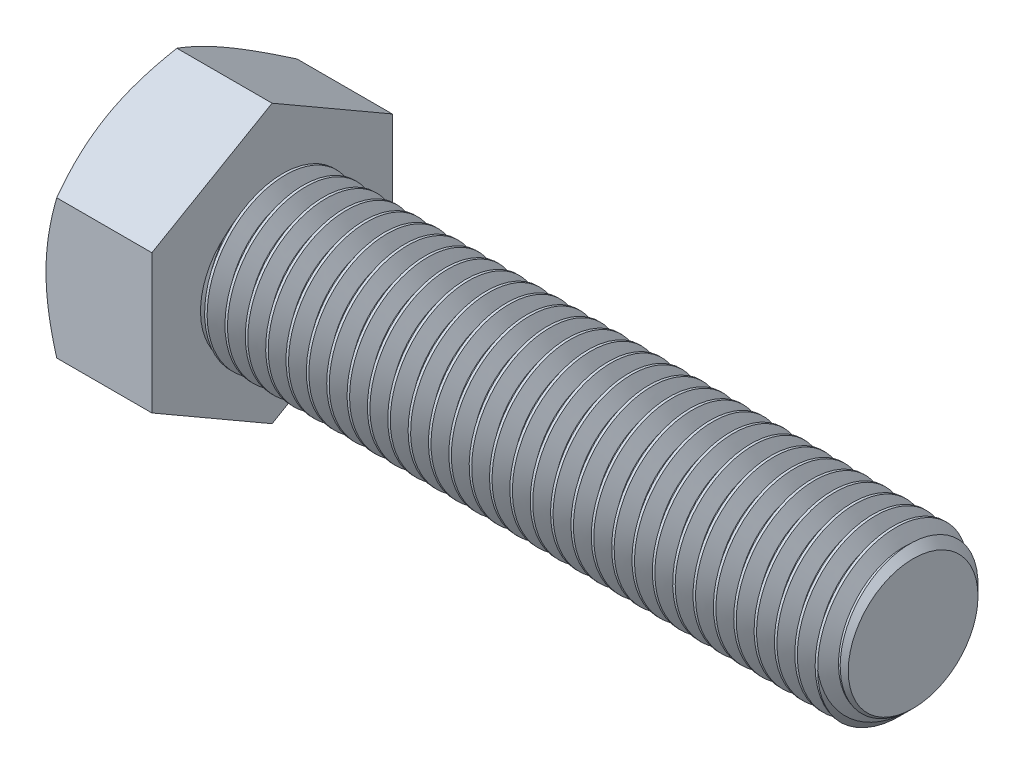
SolidWorks part; units mm, degrees
ref_plane "Front Plane" through (0, 0, 0) normal (0, 0, 1) x (1, 0, 0)
ref_plane "Top Plane" through (0, 0, 0) normal (0, 1, 0) x (1, 0, 0)
ref_plane "Right Plane" through (0, 0, 0) normal (1, 0, 0) x (0, 0, -1)
sketch "Sketch1" plane through (0, 0, 0) normal (0, 0, 1) x (1, 0, 0)
  line L0 (-51.7922, 0) -> (51.7922, 0) construction
  line L1 (51.7922, 11.1125) -> (51.7922, -11.1125) construction
  line L2 (-37.1078, 16.6687) -> (-37.1078, -16.6687) construction
  line L3 (-51.7922, 16.6687) -> (-51.7922, -16.6687) construction
  point P9 (-37.1078, 0)
  point P10 (41.9144, -11.1125)
  dimension "D1" = 9.8778
  dimension "Screw Dia" = 22.225
  dimension "Hex" = 33.3375
  dimension "Head Ht" = 14.6844
  dimension "Screw Lenght" = 88.9
ref_plane "Plane2" through (51.7922, 0, 0) normal (1, 0, 0) x (0, 0, -1)
sketch "Sketch5" plane through (51.7922, 0, 0) normal (1, 0, 0) x (0, 0, -1)
  circle A0 centre (0, 0) radius 11.1125
extrude "Boss-Extrude3" add sketch "Sketch5" against normal up to vertex (88.9 mm away) up to point (-37.1078, 0, 0)
sketch "Sketch9" plane through (51.7922, 0, 0) normal (1, 0, 0) x (0, 0, -1)
  circle A1 centre (0, 0) radius 11.1125
  circle A2 centre (0, 0) radius 11.1125
  dimension "D1" = 0
curve "Helix/Spiral1" pitch 2.8222 height 91.7222 turns 32.5 parameters "Pitch"=2.8222
chamfer "Chamfer1" distance 2.1167 angle 45 1 edges at (51.7922, 0, -11.1125)
sketch "Sketch10" plane through (0, 0, 0) normal (0, 0, 1) x (1, 0, 0)
  line L0 (51.7922, 11.1125) -> (52.8505, 9.2794)
  line L1 (52.8505, 9.2794) -> (53.2033, 9.2794)
  line L2 (53.2033, 9.2794) -> (54.2616, 11.1125)
  line L3 (51.7922, 11.1125) -> (54.2616, 11.1125)
  line L4 (53.0269, 11.1125) -> (53.0269, 9.2794) construction
  line L5 (52.3214, 10.196) -> (53.7325, 10.196) construction
  dimension "D1" = 60
  dimension "D2" = 0.3528
  dimension "D3" = 1.4111
sweep "Cut-Sweep1" cut profiles "Sketch10" path "Helix/Spiral1"
sketch "Sketch6" plane through (-37.1078, 0, 0) normal (-1, 0, 0) x (0, 0, 1)
  line L0 (0, 16.6687) -> (0, -16.6687) construction
  line L1 (16.6687, 9.6237) -> (0, 19.2474)
  line L2 (0, 19.2474) -> (-16.6687, 9.6237)
  line L3 (-16.6687, 9.6237) -> (-16.6687, -9.6237)
  line L4 (-16.6687, -9.6237) -> (0, -19.2474)
  line L5 (0, -19.2474) -> (16.6687, -9.6237)
  line L6 (16.6687, -9.6237) -> (16.6687, 9.6237)
  circle A0 centre (0, 0) radius 16.6687 construction
extrude "Boss-Extrude4" add sketch "Sketch6" along normal up to vertex (14.6844 mm away) up to point (-51.7922, -16.6687, 0)
sketch "Sketch7" plane through (-51.7922, 0, 0) normal (-1, 0, 0) x (0, 0, 1)
  circle A0 centre (0, 0) radius 16.6687 construction
  circle A1 centre (0, 0) radius 16.6687
sketch "Sketch8" plane through (-51.7922, 0, 0) normal (-1, 0, 0) x (0, 0, 1)
  circle A0 centre (0, 0) radius 16.6687 construction
  circle A1 centre (0, 0) radius 16.6687
extrude "Cut-Extrude3" cut sketch "Sketch8" against normal through all draft 60 flip side to cut
sketch "Sketch12" plane through (-51.7922, 0, 0) normal (-1, 0, 0) x (0, 0, 1)
  line L0 (0, 12.8349) -> (0, 7.1676) construction
  line L1 (0.5001, 12.8349) -> (0.5001, 7.1676)
  line L2 (-0.5001, 12.8349) -> (-0.5001, 7.1676)
  line L3 (0, 11.1125) -> (0, -11.1125) construction
  arc A0 (0.5001, 12.8349) -> (-0.5001, 12.8349) centre (0, 12.8349) ccw
  arc A1 (-0.5001, 7.1676) -> (0.5001, 7.1676) centre (0, 7.1676) ccw
  circle A3 centre (0, 0) radius 6.6675 construction
  circle A4 centre (0, 0) radius 13.335 construction
  point P2 (0, 10.0012)
  dimension "D1" = 13.335
  dimension "D3" = 26.67
  dimension "D2" = 1.0001
extrude "Cut-Extrude4" cut sketch "Sketch12" against normal blind 0.254
pattern_circular "CirPattern1" count 6 over 360 about axis through (0, 0, 0) along (1, 0, 0) of "Cut-Extrude4"
equation "\"D2@Sketch10\" = \"Pitch@Helix/Spiral1\"*.125"
equation "\"D3@Sketch10\" = \"Pitch@Helix/Spiral1\"*.5"
equation "\"D3@Helix/Spiral1\" = \"Screw Lenght@Sketch1\"+\"Pitch@Helix/Spiral1\""
equation "\"D1@Chamfer1\" = \"Pitch@Helix/Spiral1\"*.75"
equation "\"D1@Sketch12\" = \"Hex@Sketch1\"*.4"
equation "\"D3@Sketch12\" = \"Hex@Sketch1\"*.8"
equation "\"D2@Sketch12\" = \"Hex@Sketch1\"*.03"
equation "\"D1@Sketch1\" = \"Pitch@Helix/Spiral1\"*3.5"
